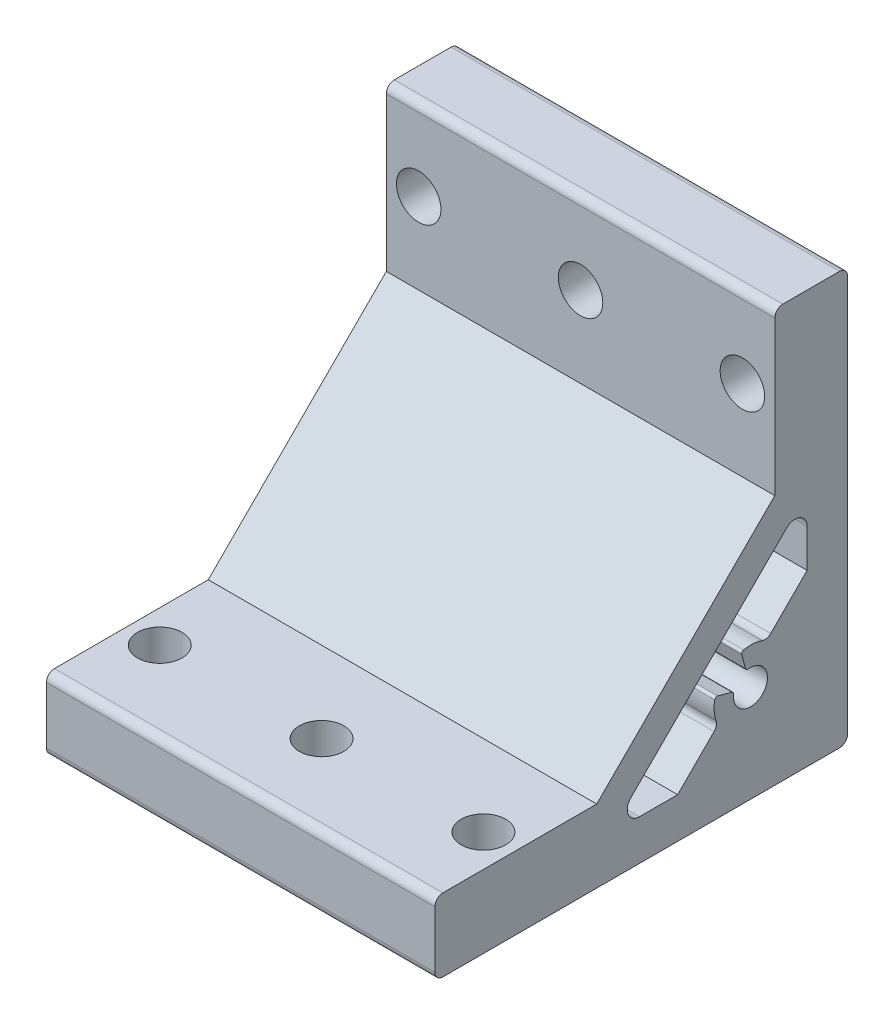
SolidWorks part; units mm, degrees
ref_plane "Front Plane" through (0, 0, 0) normal (0, 0, 1) x (1, 0, 0)
ref_plane "Top Plane" through (0, 0, 0) normal (0, 1, 0) x (1, 0, 0)
ref_plane "Right Plane" through (0, 0, 0) normal (1, 0, 0) x (0, 0, -1)
ref_plane "Plane1" through (0, 0, 0) normal (1, 0, 0) x (0, 0, -1)
sketch "Sketch1" plane through (0, 0, 0) normal (1, 0, 0) x (0, 0, -1)
  line L0 (-50, 0) -> (-1, 0)
  line L1 (0, 1) -> (0, 50)
  line L2 (-1, 51) -> (-8, 51)
  line L3 (-9, 50) -> (-9, 31)
  line L4 (-9, 31) -> (-31, 9)
  line L5 (-31, 9) -> (-50, 9)
  line L6 (-51, 8) -> (-51, 1)
  line L7 (-25.7218, 5) -> (-20.9993, 5)
  line L8 (-20.9993, 5) -> (-16.494, 9.5052)
  line L9 (-16.0465, 13.0843) -> (-14.3, 12.6163)
  line L10 (-12.6163, 14.3) -> (-13.0843, 16.0465)
  line L11 (-9.5052, 16.494) -> (-5, 20.9993)
  line L12 (-5, 20.9993) -> (-5, 25.7218)
  line L13 (-7.5607, 26.7825) -> (-26.7825, 7.5607)
  line L14 (-1, 0) -> (0, 0) construction
  line L15 (0, 0) -> (0, 1) construction
  line L16 (-1, 1) -> (-40.8569, 40.8569) construction
  arc A0 (-51, 1) -> (-50, 0) centre (-50, 1) ccw
  arc A1 (-1, 0) -> (0, 1) centre (-1, 1) ccw
  arc A2 (0, 50) -> (-1, 51) centre (-1, 50) ccw
  arc A3 (-8, 51) -> (-9, 50) centre (-8, 50) ccw
  arc A4 (-50, 9) -> (-51, 8) centre (-50, 8) ccw
  arc A5 (-26.7825, 7.5607) -> (-25.7218, 5) centre (-25.7218, 6.5) ccw
  arc A6 (-16.494, 9.5052) -> (-16.2556, 10.5372) centre (-17.2013, 10.2122) ccw
  arc A7 (-16.2556, 10.5372) -> (-16.4188, 12.8512) centre (-12, 12) cw
  arc A8 (-16.4188, 12.8512) -> (-16.0465, 13.0843) centre (-16.1242, 12.7945) cw
  arc A9 (-14.3, 12.6163) -> (-14.0805, 12.2857) centre (-14.3777, 12.3265) cw
  arc A10 (-14.0805, 12.2857) -> (-12.2857, 14.0805) centre (-12, 12) ccw
  arc A11 (-12.2857, 14.0805) -> (-12.6163, 14.3) centre (-12.3265, 14.3777) cw
  arc A12 (-13.0843, 16.0465) -> (-12.8512, 16.4188) centre (-12.7945, 16.1242) cw
  arc A13 (-12.8512, 16.4188) -> (-10.5377, 16.2558) centre (-12, 12) cw
  arc A14 (-10.5377, 16.2558) -> (-9.5052, 16.494) centre (-10.2122, 17.2013) ccw
  arc A15 (-5, 25.7218) -> (-7.5607, 26.7825) centre (-6.5, 25.7218) ccw
  dimension "D7" = 2.1
  dimension "D13" = 4.5
  dimension "D14" = 1
  dimension "D1" = 9
  dimension "D2" = 9
  dimension "D3" = 51
  dimension "D4" = 51
  dimension "D5" = 5
  dimension "D6" = 5
  dimension "D8" = 12
  dimension "D9" = 20
  dimension "D10" = 20
  dimension "D11" = 4
  dimension "D12" = 5.9
extrude "Boss-Extrude1" add sketch "Sketch1" against normal blind 24 and the other way blind 24
ref_plane "Plane2" through (0, 0, 0) normal (0, 1, 0) x (-1, 0, 0)
sketch "Sketch2" plane through (0, 0, 0) normal (0, 1, 0) x (-1, 0, 0)
  line L0 (-24, 51) -> (24, 51) construction
  line L1 (0, 1) -> (0, 50) construction
  line L2 (-24, 1) -> (24, 1) construction
  line L3 (-24, 50) -> (24, 50) construction
  circle A0 centre (20, 41) radius 2.75
  dimension "D1" = 5.5
  dimension "D2" = 10
  dimension "D3" = 20
extrude "Cut-Extrude1" cut sketch "Sketch2" along normal blind 9
ref_plane "Plane3" through (0, 0, 0) normal (0, 1, 0) x (-1, 0, 0)
sketch "Sketch3" plane through (0, 0, 0) normal (0, 1, 0) x (-1, 0, 0)
  line L0 (-24, 51) -> (24, 51) construction
  line L1 (0, 1) -> (0, 50) construction
  line L2 (-24, 1) -> (24, 1) construction
  line L3 (-24, 50) -> (24, 50) construction
  circle A0 centre (-20, 41) radius 2.75
  dimension "D1" = 5.5
  dimension "D2" = 10
  dimension "D3" = 20
extrude "Cut-Extrude2" cut sketch "Sketch3" along normal blind 9
ref_plane "Plane4" through (0, 0, 0) normal (0, 0, 1) x (1, 0, 0)
sketch "Sketch4" plane through (0, 0, 0) normal (0, 0, 1) x (1, 0, 0)
  line L0 (24, 51) -> (-24, 51) construction
  line L1 (0, 50) -> (0, 1.4023) construction
  line L2 (24, 50) -> (-24, 50) construction
  circle A0 centre (-20, 41) radius 2.75
  dimension "D2" = 5.5
  dimension "D1" = 10
  dimension "D3" = 20
extrude "Cut-Extrude3" cut sketch "Sketch4" along normal blind 9
ref_plane "Plane5" through (0, 0, 0) normal (0, 0, 1) x (1, 0, 0)
sketch "Sketch5" plane through (0, 0, 0) normal (0, 0, 1) x (1, 0, 0)
  line L0 (24, 51) -> (-24, 51) construction
  line L1 (0, 50) -> (0, 1) construction
  line L2 (24, 50) -> (-24, 50) construction
  line L3 (24, 1) -> (-24, 1) construction
  circle A0 centre (20, 41) radius 2.75
  dimension "D1" = 5.5
  dimension "D2" = 10
  dimension "D3" = 20
extrude "Cut-Extrude4" cut sketch "Sketch5" along normal blind 9
sketch "Sketch6" plane through (0, 9, 0) normal (0, 1, 0) x (1, 0, 0)
  line L0 (0, -50) -> (0, -31) construction
  line L1 (24, -50) -> (-24, -50) construction
  line L2 (24, -31) -> (-24, -31) construction
  line L3 (24, -51) -> (-24, -51) construction
  circle A0 centre (0, -41) radius 2.75
  dimension "D1" = 5.5
  dimension "D2" = 10
extrude "Cut-Extrude5" cut sketch "Sketch6" against normal blind 10
sketch "Sketch7" plane through (0, 0, 9) normal (0, 0, 1) x (1, 0, 0)
  line L0 (0, 31) -> (0, 50) construction
  line L1 (24, 31) -> (-24, 31) construction
  line L2 (24, 50) -> (-24, 50) construction
  line L3 (24, 51) -> (-24, 51) construction
  circle A0 centre (0, 41) radius 2.75
  dimension "D1" = 5.5
  dimension "D2" = 10
extrude "Cut-Extrude6" cut sketch "Sketch7" against normal blind 10
